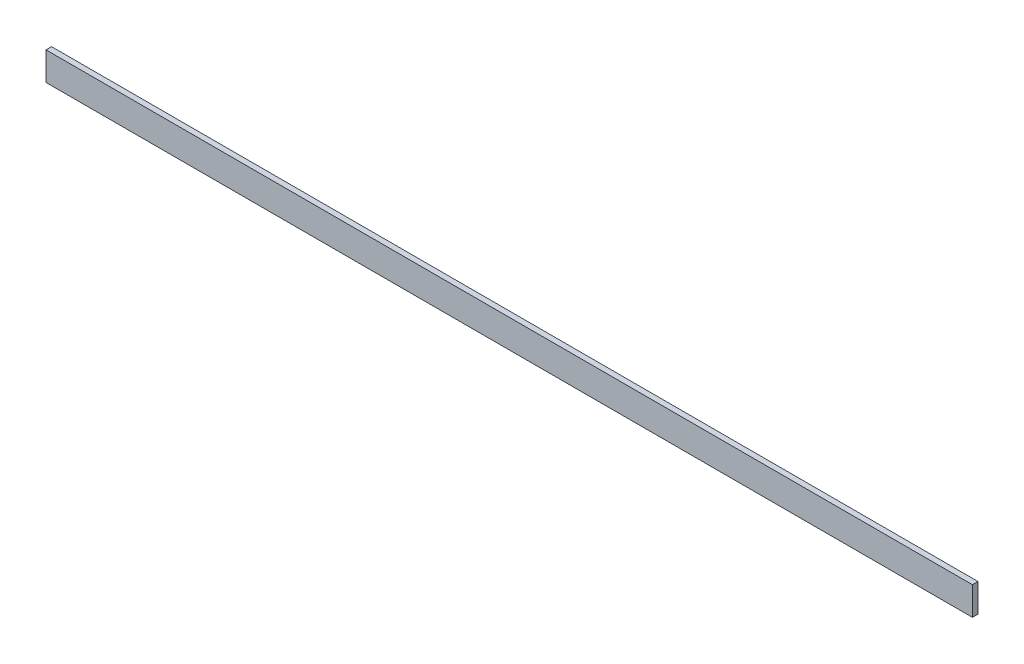
SolidWorks part; units mm, degrees
material "PC High Viscosity"
ref_plane "Front Plane" through (0, 0, 0) normal (0, 0, 1) x (1, 0, 0)
ref_plane "Top Plane" through (0, 0, 0) normal (0, 1, 0) x (1, 0, 0)
ref_plane "Right Plane" through (0, 0, 0) normal (1, 0, 0) x (0, 0, -1)
ref_axis "Axis1" through (0, -55, 0) along (0, 1, 0)
sketch "Sketch1" plane through (0, 0, 0) normal (0, 0, 1) x (1, 0, 0)
  line L1 (10.2109, -287.782) -> (0.2109, -287.782) construction
  line L4 (10.2109, -236.982) -> (0.2109, -236.982) construction
  line L6 (-917.3579, -236.982) -> (746.9373, -236.982)
  line L7 (-917.3579, -236.982) -> (-917.3579, -287.781)
  line L8 (-917.3579, -287.781) -> (746.9373, -287.781)
  line L9 (746.9373, -236.982) -> (746.9373, -287.781)
  dimension "D2" = 10
  dimension "D3" = 1664.2951
extrude "Boss-Extrude1" add sketch "Sketch1" along normal blind 10
